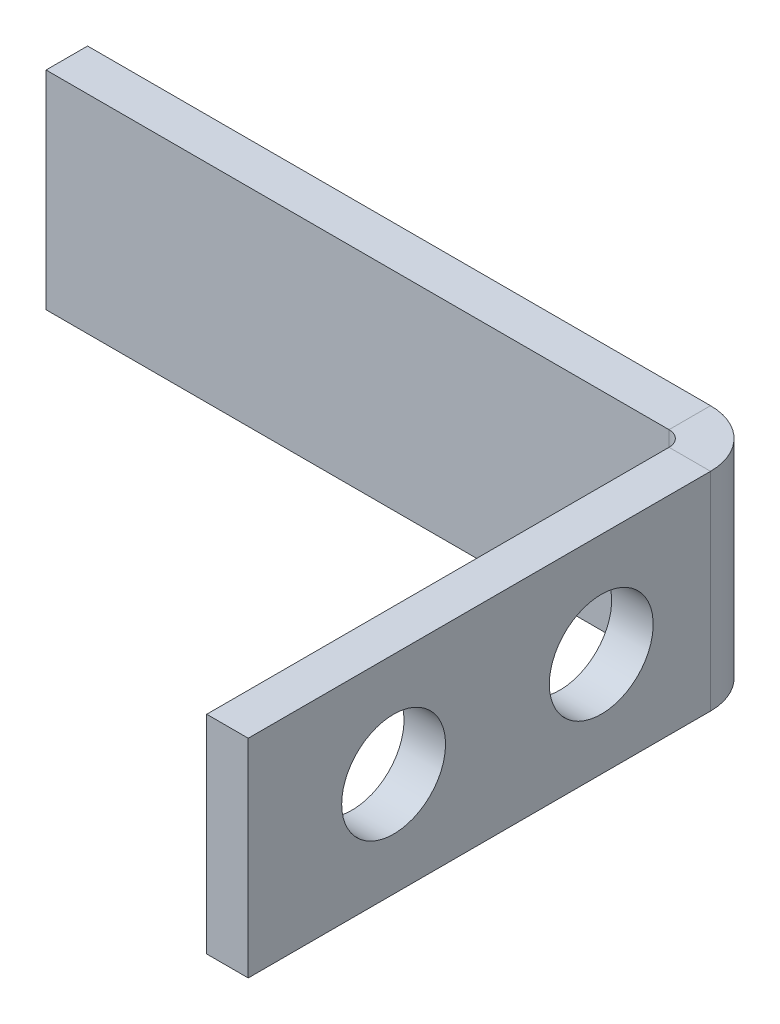
SolidWorks part; units mm, degrees
note: The reader was unsure of these and kept them because the rebuilt part matched: flange length of "Edge-Flange1".
ref_plane "Front Plane" through (0, 0, 0) normal (0, 0, 1) x (1, 0, 0)
ref_plane "Top Plane" through (0, 0, 0) normal (0, 1, 0) x (1, 0, 0)
ref_plane "Right Plane" through (0, 0, 0) normal (1, 0, 0) x (0, 0, -1)
sketch "Sketch2" plane through (0, 0, 0) normal (0, 0, 1) x (1, 0, 0)
  line L1 (-15, 5) -> (15, 5)
  line L2 (-15, 5) -> (-15, -5)
  line L3 (-15, -5) -> (15, -5)
  line L4 (15, 5) -> (15, -5)
  line L5 (-15, 5) -> (15, -5) construction
  line L6 (-15, -5) -> (15, 5) construction
  point P0 (0, 0)
  dimension "D1" = 30
  dimension "D2" = 10
base flange "Base-Flange1" sketch "Sketch2" thickness 2 reverse thickness direction no parameters "D1"=0.7366
edge flange "Edge-Flange1" sketch "Sketch9" flange angle 90 flange length 25 flange position bend outside bend radius 0.7366 thickness 2 relief rectangular parameters "D6"=10
sketch "Sketch9" plane through (15, 0, 0) normal (-1, 0, 0) x (0, -1, 0)
  line L2 (-5, 0) -> (-5, 23)
  line L3 (-5, 23) -> (5, 23)
  line L4 (5, 23) -> (5, 0)
  line L5 (5, 0) -> (-5, 0) construction
  line L6 (5, 0) -> (-5, 0)
bend "EdgeBend1" bend radius 0.7366 bend angle 90 parameters "D5"=1
sketch "Sketch10" plane through (15.7366, 0, 0) normal (-1, 0, 0) x (0, 0, 1)
  circle A0 centre (6, 0) radius 2.5
  circle A1 centre (16, 0) radius 2.5
  point P6 (4.9244, -0.0908)
  dimension "D1" = 5
  dimension "D2" = 5
  dimension "D3" = 10
  dimension "D4" = 6
extrude "Cut-Extrude1" cut sketch "Sketch10" against normal through all normal cut yes
sketch "Bend-Lines1" plane through (0, 0, 0) normal (0, 1, 0) x (1, 0, 0)
sketch "Bounding-Box1" plane through (0, 0, 0) normal (0, 1, 0) x (1, 0, 0)
sheet metal parameters "Sheet-Metal1" thickness 2 parameters "D1"=0.7366
flat pattern "Flat-Pattern1" [suppressed]
sketch "Bend-Lines2" plane through (0, 0, 0) normal (0, 1, 0) x (1, 0, 0)
sketch "Bounding-Box2" [suppressed] plane through (0, 0, 0) normal (0, 1, 0) x (1, 0, 0)
sheet metal parameters "Sheet-Metal2" thickness 2 parameters "D1"=0.7366
flat pattern "Flat-Pattern1" [suppressed]
sketch "Bend-Lines2" plane through (0, 0, 0) normal (0, 1, 0) x (1, 0, 0)
sketch "Bounding-Box2" [suppressed] plane through (0, 0, 0) normal (0, 1, 0) x (1, 0, 0)
bend of the flat pattern "Flatten-<EdgeBend1>1"
sheet metal parameters "Sheet-Metal3" thickness 2 parameters "D1"=0.7366
flat pattern "Flat-Pattern1" [suppressed]
sketch "Bend-Lines2" plane through (0, 0, 0) normal (0, 1, 0) x (1, 0, 0)
sketch "Bounding-Box2" [suppressed] plane through (0, 0, 0) normal (0, 1, 0) x (1, 0, 0)
bend of the flat pattern "Flatten-<EdgeBend1>1"
